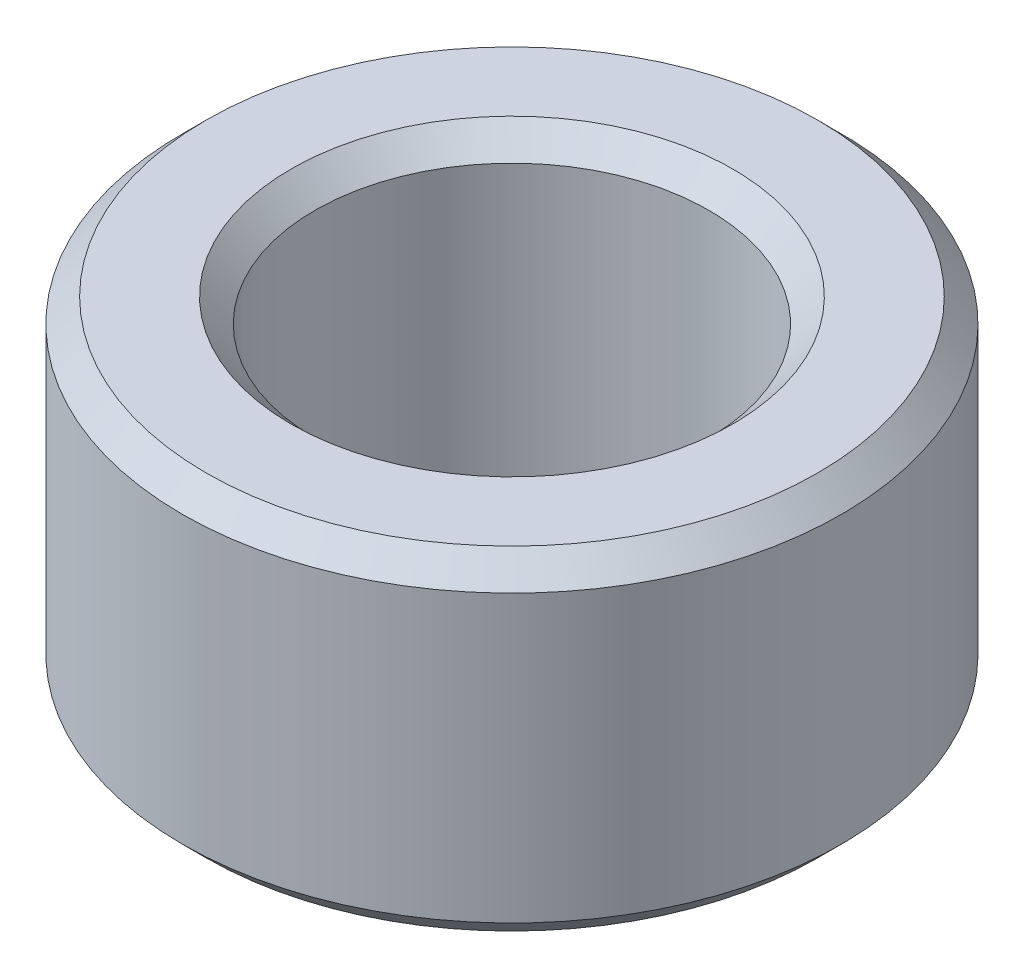
SolidWorks part; units mm, degrees
ref_plane "Front Plane" through (0, 0, 0) normal (0, 0, 1) x (1, 0, 0)
ref_plane "Top Plane" through (0, 0, 0) normal (0, 1, 0) x (1, 0, 0)
ref_plane "Right Plane" through (0, 0, 0) normal (1, 0, 0) x (0, 0, -1)
sketch "Sketch1" plane through (0, 0, 0) normal (0, 1, 0) x (1, 0, 0)
  circle A0 centre (0, 0) radius 42.5
  dimension "SLEEVE_OD" = 85
extrude "Boss-Extrude1" add sketch "Sketch1" along normal blind 42.9916
sketch "Sketch2" plane through (0, 0, 0) normal (0, 1, 0) x (1, 0, 0)
  circle A0 centre (0, 0) radius 25.4116
  dimension "BORE_D" = 50.8232
extrude "Cut-Extrude1" cut sketch "Sketch2" along normal through all
chamfer "Chamfer1" distance 3.0768 angle 45 4 edges at (0, 42.9916, 25.4116) (0, 0, 25.4116) (0, 0, 42.5) (0, 42.9916, 42.5)
